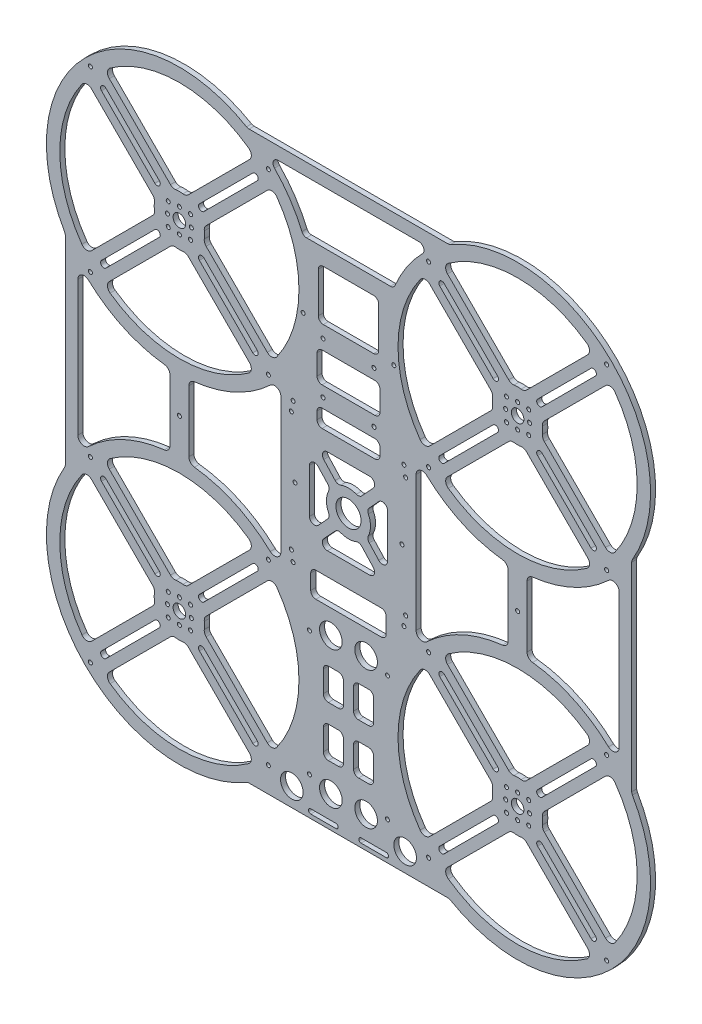
SolidWorks part; units mm, degrees
ref_plane "前视基准面" through (0, 0, 0) normal (0, 0, 1) x (1, 0, 0)
ref_plane "上视基准面" through (0, 0, 0) normal (0, 1, 0) x (1, 0, 0)
ref_plane "右视基准面" through (0, 0, 0) normal (1, 0, 0) x (0, 0, -1)
sketch "草图1" plane through (0, 0, 0) normal (0, 0, 1) x (1, 0, 0)
  line L1 (-155, 155) -> (155, 155)
  line L2 (-155, 155) -> (-155, -155)
  line L3 (-155, -155) -> (155, -155)
  line L4 (155, 155) -> (155, -155)
  line L5 (-155, 155) -> (155, -155) construction
  line L6 (-155, -155) -> (155, 155) construction
  point P0 (0, 0)
  dimension "D1" = 310
  dimension "D2" = 310
extrude "凸台-拉伸1" add sketch "草图1" along normal blind 4
sketch "草图2" plane through (0, 0, 4) normal (0, 0, 1) x (1, 0, 0)
  line L0 (-155, 0) -> (155, 0) construction
  line L1 (-155, 155) -> (-155, -155) construction
  line L2 (155, -155) -> (155, 155) construction
  line L3 (0, 155) -> (0, -155) construction
  line L4 (155, 155) -> (-155, 155) construction
  line L5 (-155, -155) -> (155, -155) construction
  line L6 (-155, -155) -> (155, 155) construction
  line L7 (-155, 155) -> (155, -155) construction
  line L8 (-134.3503, 134.3503) -> (134.3503, 134.3503) construction
  line L9 (-134.3503, 134.3503) -> (134.3503, 134.3503) construction
  line L10 (-134.3503, 134.3503) -> (-134.3503, -134.3503) construction
  line L11 (-134.3503, -134.3503) -> (134.3503, -134.3503) construction
  line L12 (134.3503, 134.3503) -> (134.3503, -134.3503) construction
  line L13 (-134.3503, 134.3503) -> (134.3503, -134.3503) construction
  line L14 (-134.3503, -134.3503) -> (134.3503, 134.3503) construction
  circle A0 centre (-134.3503, -134.3503) radius 20 construction
  circle A1 centre (-134.3503, -134.3503) radius 5
  circle A2 centre (-134.3503, -134.3503) radius 9.5 construction
  circle A3 centre (-134.3503, -143.8503) radius 1.6
  circle A4 centre (-143.8503, -134.3503) radius 1.6
  circle A5 centre (-134.3503, -124.8503) radius 1.6
  circle A6 centre (-124.8503, -134.3503) radius 1.6
  circle A7 centre (134.3503, -134.3503) radius 9.5 construction
  circle A8 centre (134.3503, -134.3503) radius 20 construction
  circle A9 centre (124.8503, -134.3503) radius 1.6
  circle A10 centre (134.3503, -124.8503) radius 1.6
  circle A11 centre (143.8503, -134.3503) radius 1.6
  circle A12 centre (134.3503, -143.8503) radius 1.6
  circle A13 centre (134.3503, -134.3503) radius 5
  circle A14 centre (134.3503, 134.3503) radius 20 construction
  circle A15 centre (134.3503, 134.3503) radius 9.5 construction
  circle A16 centre (-134.3503, 134.3503) radius 9.5 construction
  circle A17 centre (-134.3503, 134.3503) radius 20 construction
  circle A18 centre (134.3503, 134.3503) radius 5
  circle A19 centre (134.3503, 143.8503) radius 1.6
  circle A20 centre (143.8503, 134.3503) radius 1.6
  circle A21 centre (134.3503, 124.8503) radius 1.6
  circle A22 centre (124.8503, 134.3503) radius 1.6
  circle A23 centre (-124.8503, 134.3503) radius 1.6
  circle A24 centre (-134.3503, 124.8503) radius 1.6
  circle A25 centre (-143.8503, 134.3503) radius 1.6
  circle A26 centre (-134.3503, 143.8503) radius 1.6
  circle A27 centre (-134.3503, 134.3503) radius 5
  point P20 (0, 0)
  point P39 (-134.3503, -134.3503)
  point P48 (134.3503, -134.3503)
  point P71 (134.3503, 134.3503)
  point P72 (-134.3503, 134.3503)
  dimension "D3" = 40
  dimension "D4" = 10
  dimension "D5" = 19
  dimension "D6" = 3.2
  dimension "D8" = 19
  dimension "D9" = 9.5
  dimension "D1" = 380
  dimension "D2" = 268.7006
  dimension "D7" = 4
extrude "切除-拉伸2" cut sketch "草图2" against normal blind 4
sketch "草图3" plane through (0, 0, 4) normal (0, 0, 1) x (1, 0, 0)
  line L2 (-155, 0) -> (155, 0) construction
  line L3 (-155, 155) -> (-155, -155) construction
  line L4 (155, -155) -> (155, 155) construction
  line L5 (0, 155) -> (0, -155) construction
  line L6 (155, 155) -> (-155, 155) construction
  line L7 (-155, -155) -> (155, -155) construction
  circle A4 centre (0, 0) radius 2.5
  dimension "D1" = 5
extrude "切除-拉伸3" cut sketch "草图3" against normal blind 4
sketch "草图4" plane through (0, 0, 4) normal (0, 0, 1) x (1, 0, 0)
  circle A0 centre (0, 0) radius 10
  dimension "D1" = 20
extrude "切除-拉伸4" cut sketch "草图4" against normal blind 10
sketch "草图5" plane through (0, 0, 4) normal (0, 0, 1) x (1, 0, 0)
  line L0 (-155, 0) -> (155, 0) construction
  line L1 (-155, 155) -> (-155, -155) construction
  line L2 (155, -155) -> (155, 155) construction
  line L3 (0, 155) -> (0, -155) construction
  line L4 (155, 155) -> (-155, 155) construction
  line L5 (-155, -155) -> (155, -155) construction
  circle A0 centre (-42.5, 0) radius 1.6
  circle A1 centre (42.5, 0) radius 1.6
  dimension "D1" = 85
  dimension "D2" = 42.5
  dimension "D3" = 3.2
  dimension "D4" = 3.2
extrude "切除-拉伸5" cut sketch "草图5" against normal blind 10
sketch "草图7" plane through (0, 0, 4) normal (0, 0, 1) x (1, 0, 0)
  line L0 (0, 0) -> (0, 47.5) construction
  line L1 (-45.4, 47.5) -> (45.4, 47.5) construction
  line L2 (-45.4, 47.5) -> (-45.4, -47.5) construction
  line L3 (-45.4, -47.5) -> (45.4, -47.5) construction
  line L4 (45.4, 47.5) -> (45.4, -47.5) construction
  line L5 (-45.4, 47.5) -> (45.4, -47.5) construction
  line L6 (-45.4, -47.5) -> (45.4, 47.5) construction
  circle A0 centre (-45.4, 47.5) radius 1.6
  circle A1 centre (-45.4, -47.5) radius 1.6
  circle A2 centre (45.4, -47.5) radius 1.6
  circle A3 centre (45.4, 47.5) radius 1.6
  point P0 (0, 0)
  dimension "D3" = 3.2
  dimension "D4" = 3.2
  dimension "D1" = 90.8
  dimension "D2" = 95
extrude "切除-拉伸7" cut sketch "草图7" against normal blind 10
sketch "草图10" plane through (0, 0, 4) normal (0, 0, 1) x (1, 0, 0)
  line L0 (0, 0) -> (240, 0) construction
  line L1 (-240, 240) -> (240, 240) construction
  line L2 (-240, 240) -> (-240, -240) construction
  line L3 (-240, -240) -> (240, -240) construction
  line L4 (240, 240) -> (240, -240) construction
  line L5 (-240, 240) -> (240, -240) construction
  line L6 (-240, -240) -> (240, 240) construction
  line L7 (0, 0) -> (0, 155) construction
  line L8 (155, 155) -> (-155, 155) construction
  line L9 (155, -155) -> (155, 155) construction
  line L10 (155, -155) -> (-155, -155)
  line L11 (155, -155) -> (155, 155)
  line L12 (155, 155) -> (-155, 155)
  line L13 (-155, -155) -> (-155, 155)
  line L14 (155, -155) -> (-155, 155) construction
  line L15 (155, 155) -> (-155, -155) construction
  circle A0 centre (134.3503, 134.3503) radius 105.6497
  circle A1 centre (134.3503, 134.3503) radius 95
  circle A2 centre (134.3503, -134.3503) radius 95
  circle A4 centre (134.3503, -134.3503) radius 105.6497
  circle A5 centre (-134.3503, -134.3503) radius 95
  circle A6 centre (-134.3503, -134.3503) radius 105.6497
  circle A7 centre (-134.3503, 134.3503) radius 105.6497
  circle A8 centre (-134.3503, 134.3503) radius 95
  point P0 (0, 0)
  line M27 (155, 155) -> (-155, 155)
  dimension "D1" = 480
  dimension "D2" = 480
  dimension "D4" = 0
extrude "凸台-拉伸2" add sketch "草图10" against normal blind 4 contours A8 A7 L13 M27 | A6 L10 A5 L13 | L10 A4 L11 A2 | L12 A1 L11 A0 region at (145.061, -231.7224, 4) region at (-206.9633, -206.9633, 4) region at (157.9594, 36.18, 4) region at (-206.9633, 206.9633, 4)
sketch "草图11" plane through (0, 0, 4) normal (0, 0, 1) x (1, 0, 0)
  line L3 (-155, 0) -> (155, 0) construction
  line L6 (155, -30.7383) -> (155, 30.7383) construction
  line L7 (0, 155) -> (0, -155) construction
  line L8 (30.7383, 155) -> (-30.7383, 155) construction
  line L9 (-30.7383, -155) -> (30.7383, -155) construction
  line L10 (-134.3503, -134.3503) -> (134.3503, 134.3503) construction
  line L11 (-134.3503, 134.3503) -> (134.3503, -134.3503) construction
  line L21 (-155, 30.7383) -> (-155, -30.7383) construction
  line L23 (-225, 80.0871) -> (-225, -80.0871)
  line L25 (30.7383, -155) -> (-30.7383, -155)
  line L26 (-155, 30.7383) -> (-155, -30.7383)
  line L27 (-155, 30.7383) -> (-155, -30.7383)
  line L28 (80.0871, -225) -> (-80.0871, -225)
  line L29 (225, -80.0871) -> (225, 80.0871)
  line L30 (155, -30.7383) -> (155, 30.7383)
  line L31 (-30.7383, 155) -> (30.7383, 155)
  line L32 (-80.0871, 225) -> (80.0871, 225)
  arc A6 (-30.7383, 155) -> (-155, 30.7383) centre (-134.3503, 134.3503) ccw construction
  arc A7 (-155, -30.7383) -> (-30.7383, -155) centre (-134.3503, -134.3503) ccw construction
  arc A18 (80.0871, -225) -> (30.7383, -155) centre (134.3503, -134.3503) cw
  arc A19 (-30.7383, -155) -> (-80.0871, -225) centre (-134.3503, -134.3503) cw
  arc A20 (-155, -30.7383) -> (-30.7383, -155) centre (-134.3503, -134.3503) ccw
  arc A21 (-30.7383, 155) -> (-155, 30.7383) centre (-134.3503, 134.3503) ccw
  arc A22 (-155, -30.7383) -> (-225, -80.0871) centre (-134.3503, -134.3503) ccw
  arc A23 (-225, 80.0871) -> (-155, 30.7383) centre (-134.3503, 134.3503) ccw
  arc A24 (225, -80.0871) -> (155, -30.7383) centre (134.3503, -134.3503) ccw
  arc A25 (155, 30.7383) -> (225, 80.0871) centre (134.3503, 134.3503) ccw
  arc A26 (-80.0871, 225) -> (-30.7383, 155) centre (-134.3503, 134.3503) cw
  arc A27 (30.7383, 155) -> (80.0871, 225) centre (134.3503, 134.3503) cw
  dimension "D1" = 70
  dimension "D2" = 0
extrude "凸台-拉伸3" add sketch "草图11" against normal blind 4
sketch "草图12" plane through (0, 0, 4) normal (0, 0, 1) x (1, 0, 0)
  line L0 (-134.3503, -134.3503) -> (0, 0) construction
  line L1 (-74.6194, -60.4773) -> (-129.1739, -115.0318)
  line L2 (-60.4773, -74.6194) -> (-115.0318, -129.1739)
  line L3 (74.6194, -60.4773) -> (129.1739, -115.0318)
  line L4 (60.4773, -74.6194) -> (115.0318, -129.1739)
  line L5 (0, 0) -> (0, -225) construction
  line L6 (-80.0871, -225) -> (80.0871, -225) construction
  line L7 (60.4773, 74.6194) -> (115.0318, 129.1739)
  line L8 (0, 0) -> (225, 0) construction
  line L9 (225, -80.0871) -> (225, 80.0871) construction
  line L10 (74.6194, 60.4773) -> (129.1739, 115.0318)
  line L11 (-74.6194, 60.4773) -> (-129.1739, 115.0318)
  line L12 (-60.4773, 74.6194) -> (-115.0318, 129.1739)
  line L14 (-134.3503, 134.3503) -> (0, 0) construction
  arc A2 (-74.6194, -60.4773) -> (-60.4773, -74.6194) centre (-134.3503, -134.3503) ccw
  arc A3 (-129.1739, -115.0318) -> (-115.0318, -129.1739) centre (-134.3503, -134.3503) ccw
  arc A4 (74.6194, -60.4773) -> (60.4773, -74.6194) centre (134.3503, -134.3503) cw
  arc A5 (129.1739, -115.0318) -> (115.0318, -129.1739) centre (134.3503, -134.3503) cw
  arc A6 (74.6194, 60.4773) -> (60.4773, 74.6194) centre (134.3503, 134.3503) ccw
  arc A7 (129.1739, 115.0318) -> (115.0318, 129.1739) centre (134.3503, 134.3503) ccw
  arc A8 (-74.6194, 60.4773) -> (-60.4773, 74.6194) centre (-134.3503, 134.3503) cw
  arc A9 (-129.1739, 115.0318) -> (-115.0318, 129.1739) centre (-134.3503, 134.3503) cw
  dimension "D1" = 40
  dimension "D2" = 10
extrude "切除-拉伸12" cut sketch "草图12" against normal blind 6 contours L3 A5 L4 A4 | A6 L7 A7 L10 | L11 A9 L12 A8 | A3 L2 A2 L1
sketch "草图15" plane through (0, 0, 4) normal (0, 0, 1) x (1, 0, 0)
  line L10 (0, 0) -> (0, -225) construction
  line L11 (-80.0871, -225) -> (80.0871, -225) construction
  line L12 (0, 0) -> (225, 0) construction
  line L13 (225, -80.0871) -> (225, 80.0871) construction
  line L70 (60.4773, -74.6194) -> (115.0318, -129.1739) construction
  line L71 (74.6194, -60.4773) -> (129.1739, -115.0318) construction
  line L72 (194.0812, -60.4773) -> (139.5267, -115.0318)
  line L73 (208.2233, -74.6194) -> (153.6688, -129.1739)
  line L74 (208.2233, -194.0812) -> (153.6688, -139.5267)
  line L75 (194.0812, -208.2233) -> (139.5267, -153.6688)
  line L76 (74.6194, -208.2233) -> (129.1739, -153.6688)
  line L77 (60.4773, -194.0812) -> (115.0318, -139.5267)
  line L78 (-74.6194, -60.4773) -> (-129.1739, -115.0318) construction
  line L79 (-60.4773, -74.6194) -> (-115.0318, -129.1739) construction
  line L80 (-60.4773, -194.0812) -> (-115.0318, -139.5267)
  line L81 (-74.6194, -208.2233) -> (-129.1739, -153.6688)
  line L82 (-194.0812, -208.2233) -> (-139.5267, -153.6688)
  line L83 (-208.2233, -194.0812) -> (-153.6688, -139.5267)
  line L84 (-208.2233, -74.6194) -> (-153.6688, -129.1739)
  line L85 (-194.0812, -60.4773) -> (-139.5267, -115.0318)
  line L86 (-60.4773, 74.6194) -> (-115.0318, 129.1739) construction
  line L87 (-74.6194, 60.4773) -> (-129.1739, 115.0318) construction
  line L88 (74.6194, 60.4773) -> (129.1739, 115.0318) construction
  line L89 (60.4773, 74.6194) -> (115.0318, 129.1739) construction
  line L90 (-194.0812, 60.4773) -> (-139.5267, 115.0318)
  line L91 (-208.2233, 74.6194) -> (-153.6688, 129.1739)
  line L92 (-208.2233, 194.0812) -> (-153.6688, 139.5267)
  line L93 (-194.0812, 208.2233) -> (-139.5267, 153.6688)
  line L94 (-74.6194, 208.2233) -> (-129.1739, 153.6688)
  line L95 (-60.4773, 194.0812) -> (-115.0318, 139.5267)
  line L96 (60.4773, 194.0812) -> (115.0318, 139.5267)
  line L97 (74.6194, 208.2233) -> (129.1739, 153.6688)
  line L98 (194.0812, 208.2233) -> (139.5267, 153.6688)
  line L99 (208.2233, 194.0812) -> (153.6688, 139.5267)
  line L100 (208.2233, 74.6194) -> (153.6688, 129.1739)
  line L101 (194.0812, 60.4773) -> (139.5267, 115.0318)
  arc A66 (129.1739, -115.0318) -> (115.0318, -129.1739) centre (134.3503, -134.3503) ccw construction
  arc A67 (74.6194, -60.4773) -> (60.4773, -74.6194) centre (134.3503, -134.3503) ccw construction
  arc A68 (153.6688, -129.1739) -> (139.5267, -115.0318) centre (134.3503, -134.3503) ccw
  arc A69 (208.2233, -74.6194) -> (194.0812, -60.4773) centre (134.3503, -134.3503) ccw
  arc A70 (139.5267, -153.6688) -> (153.6688, -139.5267) centre (134.3503, -134.3503) ccw
  arc A71 (194.0812, -208.2233) -> (208.2233, -194.0812) centre (134.3503, -134.3503) ccw
  arc A72 (115.0318, -139.5267) -> (129.1739, -153.6688) centre (134.3503, -134.3503) ccw
  arc A73 (60.4773, -194.0812) -> (74.6194, -208.2233) centre (134.3503, -134.3503) ccw
  arc A74 (-74.6194, -60.4773) -> (-60.4773, -74.6194) centre (-134.3503, -134.3503) cw construction
  arc A75 (-129.1739, -115.0318) -> (-115.0318, -129.1739) centre (-134.3503, -134.3503) cw construction
  arc A76 (-60.4773, -194.0812) -> (-74.6194, -208.2233) centre (-134.3503, -134.3503) cw
  arc A77 (-115.0318, -139.5267) -> (-129.1739, -153.6688) centre (-134.3503, -134.3503) cw
  arc A78 (-194.0812, -208.2233) -> (-208.2233, -194.0812) centre (-134.3503, -134.3503) cw
  arc A79 (-139.5267, -153.6688) -> (-153.6688, -139.5267) centre (-134.3503, -134.3503) cw
  arc A80 (-208.2233, -74.6194) -> (-194.0812, -60.4773) centre (-134.3503, -134.3503) cw
  arc A81 (-153.6688, -129.1739) -> (-139.5267, -115.0318) centre (-134.3503, -134.3503) cw
  arc A82 (-129.1739, 115.0318) -> (-115.0318, 129.1739) centre (-134.3503, 134.3503) ccw construction
  arc A83 (-74.6194, 60.4773) -> (-60.4773, 74.6194) centre (-134.3503, 134.3503) ccw construction
  arc A84 (74.6194, 60.4773) -> (60.4773, 74.6194) centre (134.3503, 134.3503) cw construction
  arc A85 (129.1739, 115.0318) -> (115.0318, 129.1739) centre (134.3503, 134.3503) cw construction
  arc A86 (-153.6688, 129.1739) -> (-139.5267, 115.0318) centre (-134.3503, 134.3503) ccw
  arc A87 (-208.2233, 74.6194) -> (-194.0812, 60.4773) centre (-134.3503, 134.3503) ccw
  arc A88 (-139.5267, 153.6688) -> (-153.6688, 139.5267) centre (-134.3503, 134.3503) ccw
  arc A89 (-194.0812, 208.2233) -> (-208.2233, 194.0812) centre (-134.3503, 134.3503) ccw
  arc A90 (-115.0318, 139.5267) -> (-129.1739, 153.6688) centre (-134.3503, 134.3503) ccw
  arc A91 (-60.4773, 194.0812) -> (-74.6194, 208.2233) centre (-134.3503, 134.3503) ccw
  arc A92 (60.4773, 194.0812) -> (74.6194, 208.2233) centre (134.3503, 134.3503) cw
  arc A93 (115.0318, 139.5267) -> (129.1739, 153.6688) centre (134.3503, 134.3503) cw
  arc A94 (194.0812, 208.2233) -> (208.2233, 194.0812) centre (134.3503, 134.3503) cw
  arc A95 (139.5267, 153.6688) -> (153.6688, 139.5267) centre (134.3503, 134.3503) cw
  arc A96 (208.2233, 74.6194) -> (194.0812, 60.4773) centre (134.3503, 134.3503) cw
  arc A97 (153.6688, 129.1739) -> (139.5267, 115.0318) centre (134.3503, 134.3503) cw
  point P24 (134.3503, -134.3503)
  point P43 (-134.3503, -134.3503)
  point P78 (-134.3503, 134.3503)
  point P79 (134.3503, 134.3503)
  dimension "D1" = 4
extrude "凸台-拉伸4" add sketch "草图15" against normal blind 4
sketch "草图19" plane through (0, 0, 4) normal (0, 0, 1) x (1, 0, 0)
  line L1 (134.3503, -134.3503) -> (0, 0) construction
  line L2 (0, 225) -> (0, -225) construction
  line L3 (-80.0871, -225) -> (80.0871, -225) construction
  line L4 (0, 0) -> (225, 0) construction
  line L5 (225, -80.0871) -> (225, 80.0871) construction
  line L6 (-134.3503, -134.3503) -> (0, 0) construction
  line L7 (-134.3503, 134.3503) -> (0, 0) construction
  circle A0 centre (134.3503, -134.3503) radius 100 construction
  circle A1 centre (63.6396, -63.6396) radius 1.6
  circle A21 centre (205.061, -63.6396) radius 1.6
  circle A22 centre (205.061, -205.061) radius 1.6
  circle A23 centre (63.6396, -205.061) radius 1.6
  circle A24 centre (134.3503, -134.3503) radius 5 construction
  circle A25 centre (-134.3503, -134.3503) radius 100 construction
  circle A26 centre (-63.6396, -205.061) radius 1.6
  circle A27 centre (-205.061, -205.061) radius 1.6
  circle A28 centre (-205.061, -63.6396) radius 1.6
  circle A29 centre (-63.6396, -63.6396) radius 1.6
  circle A30 centre (-134.3503, 134.3503) radius 100 construction
  circle A31 centre (134.3503, 134.3503) radius 100 construction
  circle A32 centre (-63.6396, 63.6396) radius 1.6
  circle A33 centre (-205.061, 63.6396) radius 1.6
  circle A34 centre (-205.061, 205.061) radius 1.6
  circle A35 centre (-63.6396, 205.061) radius 1.6
  circle A36 centre (63.6396, 205.061) radius 1.6
  circle A37 centre (205.061, 205.061) radius 1.6
  circle A38 centre (205.061, 63.6396) radius 1.6
  circle A39 centre (63.6396, 63.6396) radius 1.6
  point P16 (134.3475, -134.9818)
  point P24 (134.3503, -134.3503)
  point P34 (-134.3503, -134.3503)
  point P35 (-134.3475, -134.9818)
  point P56 (-134.3475, 134.9818)
  point P57 (-134.3503, 134.3503)
  point P58 (134.3503, 134.3503)
  point P59 (134.3475, 134.9818)
  dimension "D1" = 200
  dimension "D2" = 3.2
  dimension "D5" = 141.4214
  dimension "D4" = 100
  dimension "D3" = 4
extrude "切除-拉伸13" cut sketch "草图19" against normal blind 6
sketch "草图20" plane through (0, 0, 4) normal (0, 0, 1) x (1, 0, 0)
  line L0 (0, 0) -> (0, -225) construction
  line L1 (-80.0871, -225) -> (80.0871, -225) construction
  line L3 (-31, -96) -> (31, -96) construction
  line L4 (-31, -96) -> (-31, -195) construction
  line L5 (-31, -195) -> (31, -195) construction
  line L6 (31, -96) -> (31, -195) construction
  line L7 (-31, -96) -> (31, -195) construction
  line L8 (-31, -195) -> (31, -96) construction
  circle A0 centre (-31, -195) radius 1.6
  circle A1 centre (-31, -96) radius 1.6
  circle A2 centre (31, -195) radius 1.6
  circle A3 centre (31, -96) radius 1.6
  point P5 (0, -145.5)
  dimension "D4" = 3.2
  dimension "D5" = 3.2
  dimension "D1" = 99
  dimension "D2" = 62
  dimension "D3" = 30
extrude "切除-拉伸14" cut sketch "草图20" against normal blind 10
sketch "草图21" plane through (0, 0, 4) normal (0, 0, 1) x (1, 0, 0)
  line L0 (-225, 0) -> (225, 0) construction
  line L1 (-225, 80.0871) -> (-225, -80.0871) construction
  line L2 (225, -80.0871) -> (225, 80.0871) construction
  line L3 (0, 225) -> (0, -225) construction
  line L4 (80.0871, 225) -> (-80.0871, 225) construction
  line L5 (-80.0871, -225) -> (80.0871, -225) construction
  line L6 (-215, 66.1045) -> (-215, -66.1045)
  line L7 (-134.3503, 134.3503) -> (-134.3503, -134.3503) construction
  line L8 (-141.8503, 28.9671) -> (-141.8503, -28.9671)
  line L9 (-53.7006, 66.1045) -> (-53.7006, -66.1045)
  line L10 (-126.8503, 28.9671) -> (-126.8503, -28.9671)
  line L11 (-134.3503, -134.3503) -> (134.3503, 134.3503) construction
  line L12 (126.8503, 28.9671) -> (126.8503, -28.9671)
  line L13 (53.7006, 66.1045) -> (53.7006, -66.1045)
  line L14 (141.8503, 28.9671) -> (141.8503, -28.9671)
  line L15 (215, 66.1045) -> (215, -66.1045)
  arc A1 (-215, 66.1045) -> (-141.8503, 28.9671) centre (-134.3503, 134.3503) ccw
  arc A2 (-53.7006, -66.1045) -> (-126.8503, -28.9671) centre (-134.3503, -134.3503) ccw
  arc A3 (-141.8503, -28.9671) -> (-215, -66.1045) centre (-134.3503, -134.3503) ccw
  arc A4 (-126.8503, 28.9671) -> (-53.7006, 66.1045) centre (-134.3503, 134.3503) ccw
  arc A5 (126.8503, 28.9671) -> (53.7006, 66.1045) centre (134.3503, 134.3503) cw
  arc A6 (53.7006, -66.1045) -> (126.8503, -28.9671) centre (134.3503, -134.3503) cw
  arc A7 (215, 66.1045) -> (141.8503, 28.9671) centre (134.3503, 134.3503) cw
  arc A8 (141.8503, -28.9671) -> (215, -66.1045) centre (134.3503, -134.3503) cw
  dimension "D1" = 10
  dimension "D2" = 7.5
extrude "切除-拉伸15" cut sketch "草图21" against normal blind 10
fillet "圆角1" radius 5 80 edges at (-60.4773, 74.6194, 2) (-115.0318, 129.1739, 2) (-115.0318, 139.5267, 2) (-60.4773, 194.0812, 2) (129.1739, 115.0318, 2) (139.5267, 115.0318, 2) (194.0812, 60.4773, 2) (74.6194, 60.4773, 2) (-129.1739, -115.0318, 2) (-139.5267, -115.0318, 2) (-194.0812, -60.4773, 2) (-74.6194, -60.4773, 2) (60.4773, -74.6194, 2) (115.0318, -129.1739, 2) (115.0318, -139.5267, 2) (60.4773, -194.0812, 2) (139.5267, -115.0318, 2) (129.1739, -115.0318, 2) (74.6194, -60.4773, 2) (194.0812, -60.4773, 2) (153.6688, -139.5267, 2) (153.6688, -129.1739, 2) (208.2233, -74.6194, 2) (208.2233, -194.0812, 2) (129.1739, -153.6688, 2) (139.5267, -153.6688, 2) (194.0812, -208.2233, 2) (74.6194, -208.2233, 2) (-115.0318, -139.5267, 2) (-115.0318, -129.1739, 2) (-60.4773, -74.6194, 2) (-60.4773, -194.0812, 2) (-139.5267, -153.6688, 2) (-129.1739, -153.6688, 2) (-74.6194, -208.2233, 2) (-194.0812, -208.2233, 2) (-153.6688, -129.1739, 2) (-153.6688, -139.5267, 2) (-208.2233, -194.0812, 2) (-208.2233, -74.6194, 2) (-139.5267, 115.0318, 2) (-129.1739, 115.0318, 2) (-74.6194, 60.4773, 2) (-194.0812, 60.4773, 2) (-153.6688, 129.1739, 2) (-208.2233, 74.6194, 2) (-208.2233, 194.0812, 2) (-129.1739, 153.6688, 2) (-139.5267, 153.6688, 2) (-194.0812, 208.2233, 2) (-74.6194, 208.2233, 2) (115.0318, 139.5267, 2) (115.0318, 129.1739, 2) (60.4773, 74.6194, 2) (60.4773, 194.0812, 2) (139.5267, 153.6688, 2) (129.1739, 153.6688, 2) (74.6194, 208.2233, 2) (194.0812, 208.2233, 2) (153.6688, 129.1739, 2) (153.6688, 139.5267, 2) (208.2233, 194.0812, 2) (208.2233, 74.6194, 2) (126.8503, -28.9671, 2) (53.7006, -66.1045, 2) (53.7006, 66.1045, 2) (126.8503, 28.9671, 2) (-141.8503, -28.9671, 2) (-215, -66.1045, 2) (-215, 66.1045, 2) (-141.8503, 28.9671, 2) (-53.7006, -66.1045, 2) (-126.8503, -28.9671, 2) (-126.8503, 28.9671, 2) (-53.7006, 66.1045, 2) (215, -66.1045, 2) (141.8503, -28.9671, 2) (141.8503, 28.9671, 2) (215, 66.1045, 2) (-153.6688, 139.5267, 2)
sketch "草图24" plane through (0, 0, 4) normal (0, 0, 1) x (1, 0, 0)
  line L0 (-225, 0) -> (225, 0) construction
  line L1 (-225, 80.0871) -> (-225, -80.0871) construction
  line L2 (225, -80.0871) -> (225, 80.0871) construction
  line L3 (0, 225) -> (0, -225) construction
  line L4 (80.0871, 225) -> (-80.0871, 225) construction
  line L5 (-80.0871, -225) -> (80.0871, -225) construction
  line L6 (-205.061, -205.061) -> (-134.3503, -134.3503) construction
  line L7 (-194.4544, -194.4544) -> (-152.028, -152.028) construction
  line L8 (-196.2221, -192.6866) -> (-153.7957, -150.2602)
  line L9 (-192.6866, -196.2221) -> (-150.2602, -153.7957)
  line L10 (-196.2221, -76.014) -> (-153.7957, -118.4404)
  line L11 (-192.6866, -72.4784) -> (-150.2602, -114.9049)
  line L12 (-194.4544, -74.2462) -> (-152.028, -116.6726) construction
  line L13 (-76.014, -72.4784) -> (-118.4404, -114.9049)
  line L14 (-72.4784, -76.014) -> (-114.9049, -118.4404)
  line L15 (-74.2462, -74.2462) -> (-116.6726, -116.6726) construction
  line L16 (-72.4784, -192.6866) -> (-114.9049, -150.2602)
  line L17 (-76.014, -196.2221) -> (-118.4404, -153.7957)
  line L18 (-74.2462, -194.4544) -> (-116.6726, -152.028) construction
  line L19 (205.061, -205.061) -> (134.3503, -134.3503) construction
  line L20 (74.2462, -194.4544) -> (116.6726, -152.028) construction
  line L21 (76.014, -196.2221) -> (118.4404, -153.7957)
  line L22 (72.4784, -192.6866) -> (114.9049, -150.2602)
  line L23 (74.2462, -74.2462) -> (116.6726, -116.6726) construction
  line L24 (72.4784, -76.014) -> (114.9049, -118.4404)
  line L25 (76.014, -72.4784) -> (118.4404, -114.9049)
  line L26 (194.4544, -74.2462) -> (152.028, -116.6726) construction
  line L27 (192.6866, -72.4784) -> (150.2602, -114.9049)
  line L28 (196.2221, -76.014) -> (153.7957, -118.4404)
  line L29 (194.4544, -194.4544) -> (152.028, -152.028) construction
  line L30 (196.2221, -192.6866) -> (153.7957, -150.2602)
  line L31 (192.6866, -196.2221) -> (150.2602, -153.7957)
  line L32 (205.061, 205.061) -> (134.3503, 134.3503) construction
  line L33 (-205.061, 205.061) -> (-134.3503, 134.3503) construction
  line L34 (194.4544, 194.4544) -> (152.028, 152.028) construction
  line L35 (196.2221, 192.6866) -> (153.7957, 150.2602)
  line L36 (192.6866, 196.2221) -> (150.2602, 153.7957)
  line L37 (194.4544, 74.2462) -> (152.028, 116.6726) construction
  line L38 (192.6866, 72.4784) -> (150.2602, 114.9049)
  line L39 (196.2221, 76.014) -> (153.7957, 118.4404)
  line L40 (74.2462, 74.2462) -> (116.6726, 116.6726) construction
  line L41 (72.4784, 76.014) -> (114.9049, 118.4404)
  line L42 (76.014, 72.4784) -> (118.4404, 114.9049)
  line L43 (74.2462, 194.4544) -> (116.6726, 152.028) construction
  line L44 (76.014, 196.2221) -> (118.4404, 153.7957)
  line L45 (72.4784, 192.6866) -> (114.9049, 150.2602)
  line L46 (-74.2462, 194.4544) -> (-116.6726, 152.028) construction
  line L47 (-76.014, 196.2221) -> (-118.4404, 153.7957)
  line L48 (-72.4784, 192.6866) -> (-114.9049, 150.2602)
  line L49 (-74.2462, 74.2462) -> (-116.6726, 116.6726) construction
  line L50 (-72.4784, 76.014) -> (-114.9049, 118.4404)
  line L51 (-76.014, 72.4784) -> (-118.4404, 114.9049)
  line L52 (-194.4544, 74.2462) -> (-152.028, 116.6726) construction
  line L53 (-192.6866, 72.4784) -> (-150.2602, 114.9049)
  line L54 (-196.2221, 76.014) -> (-153.7957, 118.4404)
  line L55 (-194.4544, 194.4544) -> (-152.028, 152.028) construction
  line L56 (-196.2221, 192.6866) -> (-153.7957, 150.2602)
  line L57 (-192.6866, 196.2221) -> (-150.2602, 153.7957)
  circle A0 centre (-134.3503, -134.3503) radius 20 construction
  arc A1 (-196.2221, -192.6866) -> (-192.6866, -196.2221) centre (-194.4544, -194.4544) ccw
  arc A2 (-150.2602, -153.7957) -> (-153.7957, -150.2602) centre (-152.028, -152.028) ccw
  circle A3 centre (-134.3503, -134.3503) radius 5 construction
  circle A4 centre (-205.061, -205.061) radius 1.6 construction
  arc A5 (-192.6866, -72.4784) -> (-196.2221, -76.014) centre (-194.4544, -74.2462) ccw
  arc A6 (-153.7957, -118.4404) -> (-150.2602, -114.9049) centre (-152.028, -116.6726) ccw
  arc A7 (-72.4784, -76.014) -> (-76.014, -72.4784) centre (-74.2462, -74.2462) ccw
  arc A8 (-118.4404, -114.9049) -> (-114.9049, -118.4404) centre (-116.6726, -116.6726) ccw
  arc A9 (-76.014, -196.2221) -> (-72.4784, -192.6866) centre (-74.2462, -194.4544) ccw
  arc A10 (-114.9049, -150.2602) -> (-118.4404, -153.7957) centre (-116.6726, -152.028) ccw
  circle A11 centre (134.3503, -134.3503) radius 20 construction
  arc A12 (76.014, -196.2221) -> (72.4784, -192.6866) centre (74.2462, -194.4544) cw
  arc A13 (114.9049, -150.2602) -> (118.4404, -153.7957) centre (116.6726, -152.028) cw
  arc A14 (72.4784, -76.014) -> (76.014, -72.4784) centre (74.2462, -74.2462) cw
  arc A15 (118.4404, -114.9049) -> (114.9049, -118.4404) centre (116.6726, -116.6726) cw
  arc A16 (192.6866, -72.4784) -> (196.2221, -76.014) centre (194.4544, -74.2462) cw
  arc A17 (153.7957, -118.4404) -> (150.2602, -114.9049) centre (152.028, -116.6726) cw
  arc A18 (196.2221, -192.6866) -> (192.6866, -196.2221) centre (194.4544, -194.4544) cw
  arc A19 (150.2602, -153.7957) -> (153.7957, -150.2602) centre (152.028, -152.028) cw
  circle A20 centre (134.3503, 134.3503) radius 20 construction
  circle A21 centre (-134.3503, 134.3503) radius 20 construction
  arc A22 (196.2221, 192.6866) -> (192.6866, 196.2221) centre (194.4544, 194.4544) ccw
  arc A23 (150.2602, 153.7957) -> (153.7957, 150.2602) centre (152.028, 152.028) ccw
  arc A24 (192.6866, 72.4784) -> (196.2221, 76.014) centre (194.4544, 74.2462) ccw
  arc A25 (153.7957, 118.4404) -> (150.2602, 114.9049) centre (152.028, 116.6726) ccw
  arc A26 (72.4784, 76.014) -> (76.014, 72.4784) centre (74.2462, 74.2462) ccw
  arc A27 (118.4404, 114.9049) -> (114.9049, 118.4404) centre (116.6726, 116.6726) ccw
  arc A28 (76.014, 196.2221) -> (72.4784, 192.6866) centre (74.2462, 194.4544) ccw
  arc A29 (114.9049, 150.2602) -> (118.4404, 153.7957) centre (116.6726, 152.028) ccw
  arc A30 (-76.014, 196.2221) -> (-72.4784, 192.6866) centre (-74.2462, 194.4544) cw
  arc A31 (-114.9049, 150.2602) -> (-118.4404, 153.7957) centre (-116.6726, 152.028) cw
  arc A32 (-72.4784, 76.014) -> (-76.014, 72.4784) centre (-74.2462, 74.2462) cw
  arc A33 (-118.4404, 114.9049) -> (-114.9049, 118.4404) centre (-116.6726, 116.6726) cw
  arc A34 (-192.6866, 72.4784) -> (-196.2221, 76.014) centre (-194.4544, 74.2462) cw
  arc A35 (-153.7957, 118.4404) -> (-150.2602, 114.9049) centre (-152.028, 116.6726) cw
  arc A36 (-196.2221, 192.6866) -> (-192.6866, 196.2221) centre (-194.4544, 194.4544) cw
  arc A37 (-150.2602, 153.7957) -> (-153.7957, 150.2602) centre (-152.028, 152.028) cw
  point P19 (-173.2412, -173.2412)
  point P33 (-173.2412, -95.4594)
  point P40 (-95.4594, -95.4594)
  point P47 (-95.4594, -173.2412)
  point P52 (-134.3503, -134.3503)
  point P53 (134.3503, -134.3503)
  point P56 (95.4594, -173.2412)
  point P63 (95.4594, -95.4594)
  point P70 (173.2412, -95.4594)
  point P77 (173.2412, -173.2412)
  point P90 (173.2412, 173.2412)
  point P97 (173.2412, 95.4594)
  point P104 (95.4594, 95.4594)
  point P111 (95.4594, 173.2412)
  point P116 (134.3503, 134.3503)
  point P117 (-134.3503, 134.3503)
  point P120 (-95.4594, 173.2412)
  point P127 (-95.4594, 95.4594)
  point P134 (-173.2412, 95.4594)
  point P141 (-173.2412, 173.2412)
  dimension "D1" = 40
  dimension "D2" = 2.5
  dimension "D3" = 25
  dimension "D4" = 15
  dimension "D6" = 17.6777
  dimension "D7" = 17.6777
  dimension "D5" = 4
extrude "切除-拉伸16" cut sketch "草图24" against normal blind 10
sketch "草图25" plane through (0, 0, 4) normal (0, 0, 1) x (1, 0, 0)
  line L0 (-63.6396, -205.061) -> (63.6396, -205.061) construction
  line L1 (0, -225) -> (0, 225) construction
  line L2 (-80.0871, -225) -> (80.0871, -225) construction
  line L3 (80.0871, 225) -> (-80.0871, 225) construction
  line L4 (-30, -220) -> (-10, -220) construction
  line L5 (-30, -218.2) -> (-10, -218.2)
  line L6 (-30, -221.8) -> (-10, -221.8)
  line L7 (30, -220) -> (10, -220) construction
  line L8 (30, -218.2) -> (10, -218.2)
  line L9 (30, -221.8) -> (10, -221.8)
  arc A1 (-30, -218.2) -> (-30, -221.8) centre (-30, -220) ccw
  arc A2 (-10, -221.8) -> (-10, -218.2) centre (-10, -220) ccw
  arc A3 (30, -218.2) -> (30, -221.8) centre (30, -220) cw
  arc A4 (10, -221.8) -> (10, -218.2) centre (10, -220) cw
  point P12 (-20, -220)
  point P19 (20, -220)
  dimension "D1" = 1.8
  dimension "D2" = 10
  dimension "D3" = 5
  dimension "D4" = 20
extrude "切除-拉伸17" cut sketch "草图25" against normal blind 5
sketch "草图26" plane through (0, 0, 4) normal (0, 0, 1) x (1, 0, 0)
  line L0 (0, 225) -> (0, -225) construction
  line L1 (80.0871, 225) -> (-80.0871, 225) construction
  line L2 (-80.0871, -225) -> (80.0871, -225) construction
  line L3 (-225, 0) -> (225, 0) construction
  line L4 (-225, 80.0871) -> (-225, -80.0871) construction
  line L5 (225, -80.0871) -> (225, 80.0871) construction
  line L7 (-20.25, 110.25) -> (20.25, 110.25) construction
  line L8 (-20.25, 110.25) -> (-20.25, 69.75) construction
  line L9 (-20.25, 69.75) -> (20.25, 69.75) construction
  line L10 (20.25, 110.25) -> (20.25, 69.75) construction
  line L11 (-20.25, 110.25) -> (20.25, 69.75) construction
  line L12 (-20.25, 69.75) -> (20.25, 110.25) construction
  circle A0 centre (-20.25, 69.75) radius 1.6
  circle A1 centre (-20.25, 110.25) radius 1.6
  circle A2 centre (20.25, 69.75) radius 1.6
  circle A3 centre (20.25, 110.25) radius 1.6
  circle A4 centre (-36, 120) radius 1.6
  circle A5 centre (36, 120) radius 1.6
  point P12 (0, 90)
  dimension "D4" = 3.2
  dimension "D5" = 3.2
  dimension "D6" = 36
  dimension "D7" = 3.2
  dimension "D8" = 120
  dimension "D1" = 90
  dimension "D2" = 40.5
  dimension "D3" = 40.5
extrude "切除-拉伸18" cut sketch "草图26" against normal blind 10
sketch "草图27" plane through (0, 0, 4) normal (0, 0, 1) x (1, 0, 0)
  line L0 (-225, 0) -> (225, 0) construction
  line L1 (-225, 80.0871) -> (-225, -80.0871) construction
  line L2 (225, -80.0871) -> (225, 80.0871) construction
  line L3 (0, 225) -> (0, -225) construction
  line L4 (80.0871, 225) -> (-80.0871, 225) construction
  line L5 (-80.0871, -225) -> (80.0871, -225) construction
  line L6 (-126.8503, 24.4089) -> (-126.8503, -24.4089) construction
  line L7 (-31, -96) -> (31, -195) construction
  line L8 (0, -145.5) -> (20, -145.5) construction
  line L9 (-20, -138) -> (20, -138) construction
  line L10 (-20, -138) -> (-20, -153) construction
  line L11 (-20, -153) -> (20, -153) construction
  line L12 (20, -138) -> (20, -153) construction
  line L13 (-20, -138) -> (20, -153) construction
  line L14 (-20, -153) -> (20, -138) construction
  line L15 (-31, 27.7529) -> (-31, -27.7529)
  line L16 (-20, -178) -> (20, -178)
  line L17 (-20, -178) -> (-20, -153)
  line L18 (-20, -153) -> (20, -153)
  line L19 (20, -178) -> (20, -153)
  line L20 (-20, -178) -> (20, -153) construction
  line L21 (-20, -153) -> (20, -178) construction
  line L22 (-35, 38) -> (35, 38) construction
  line L23 (-35, 38) -> (-35, -38) construction
  line L24 (-35, -38) -> (35, -38) construction
  line L25 (35, 38) -> (35, -38) construction
  line L26 (-35, 38) -> (35, -38) construction
  line L27 (-35, -38) -> (35, 38) construction
  line L28 (-31, 27.7529) -> (-14.4841, 9.8214)
  line L29 (-31, -27.7529) -> (-14.4841, -9.8214)
  line L30 (-25.8776, -34) -> (25.8776, -34)
  line L31 (-25.8776, -34) -> (-8.5998, -15.2412)
  line L32 (25.8776, -34) -> (8.5998, -15.2412)
  line L33 (31, -27.7529) -> (14.4841, -9.8214)
  line L34 (31, 27.7529) -> (14.4841, 9.8214)
  line L35 (31, 27.7529) -> (31, -27.7529)
  line L36 (25.8776, 34) -> (8.5998, 15.2412)
  line L37 (-25.8776, 34) -> (25.8776, 34)
  line L38 (-25.8776, 34) -> (-8.5998, 15.2412)
  line L39 (-20, -138) -> (20, -138)
  line L40 (20, -113) -> (20, -138)
  line L41 (-20, -113) -> (20, -113)
  line L42 (-20, -113) -> (-20, -138)
  line L44 (-30, -52) -> (30, -52)
  line L45 (-30, -52) -> (-30, -72)
  line L46 (-30, -72) -> (30, -72)
  line L47 (30, -52) -> (30, -72)
  line L48 (-30, -52) -> (30, -72) construction
  line L49 (-30, -72) -> (30, -52) construction
  circle A0 centre (-134.3503, 0) radius 1.6
  circle A1 centre (134.3503, 0) radius 1.6
  circle A2 centre (-45, -210) radius 9
  circle A3 centre (-14, -200) radius 9
  circle A4 centre (14, -200) radius 9
  circle A5 centre (45, -210) radius 9
  circle A6 centre (14, -91) radius 9
  circle A7 centre (-14, -91) radius 9
  arc A8 (-14.4841, 9.8214) -> (-14.4841, -9.8214) centre (0, 0) ccw
  arc A9 (8.5998, 15.2412) -> (-8.5998, 15.2412) centre (0, 0) ccw
  arc A10 (14.4841, -9.8214) -> (14.4841, 9.8214) centre (0, 0) ccw
  arc A11 (-8.5998, -15.2412) -> (8.5998, -15.2412) centre (0, 0) ccw
  point P26 (0, -145.5)
  point P33 (0, -165.5)
  point P45 (0, 0)
  point P58 (-31, 0)
  point P62 (0, -34)
  point P72 (0, -62)
  dimension "D1" = 7.5
  dimension "D2" = 3.2
  dimension "D3" = 15
  dimension "D4" = 45
  dimension "D5" = 14
  dimension "D6" = 25
  dimension "D7" = 18
  dimension "D8" = 18
  dimension "D14" = 35
  dimension "D9" = 15
  dimension "D10" = 40
  dimension "D11" = 25
  dimension "D12" = 70
  dimension "D13" = 76
  dimension "D15" = 4
  dimension "D16" = 4
  dimension "D17" = 4
  dimension "D18" = 20
  dimension "D19" = 62
  dimension "D20" = 60
extrude "切除-拉伸19" cut sketch "草图27" against normal blind 10
fillet "圆角3" radius 4 28 edges at (20, -113, 2) (20, -138, 2) (-20, -138, 2) (-20, -113, 2) (-20, -178, 2) (-20, -153, 2) (20, -153, 2) (20, -178, 2) (-30, -72, 2) (30, -52, 2) (30, -72, 2) (8.5998, 15.2412, 2) (-8.5998, 15.2412, 2) (-25.8776, 34, 2) (25.8776, 34, 2) (-14.4841, -9.8214, 2) (-31, -27.7529, 2) (-31, 27.7529, 2) (-14.4841, 9.8214, 2) (14.4841, -9.8214, 2) (14.4841, 9.8214, 2) (31, 27.7529, 2) (31, -27.7529, 2) (8.5998, -15.2412, 2) (25.8776, -34, 2) (-25.8776, -34, 2) (-8.5998, -15.2412, 2) (-30, -52, 2)
sketch "草图29" plane through (0, 0, 4) normal (0, 0, 1) x (1, 0, 0)
  line L3 (-36.024, 173) -> (36.024, 173)
  line L4 (66.1045, 215) -> (-66.1045, 215)
  arc A2 (-36.024, 173) -> (-66.1045, 215) centre (-134.3503, 134.3503) ccw
  arc A3 (66.1045, 215) -> (36.024, 173) centre (134.3503, 134.3503) ccw
extrude "切除-拉伸21" cut sketch "草图29" against normal blind 10
sketch "草图30" plane through (0, 0, 4) normal (0, 0, 1) x (1, 0, 0)
  line L0 (0, 0) -> (0, -225) construction
  line L1 (-80.0871, -225) -> (80.0871, -225) construction
  line L2 (-16, -178) -> (16, -178) construction
  line L3 (-4, -113) -> (4, -113)
  line L4 (-4, -113) -> (-4, -178)
  line L5 (-4, -178) -> (4, -178)
  line L6 (4, -113) -> (4, -178)
  line L7 (-4, -113) -> (4, -178) construction
  line L8 (-4, -178) -> (4, -113) construction
  line L9 (16, -113) -> (-16, -113) construction
  point P5 (0, -145.5)
  dimension "D1" = 0
  dimension "D2" = 8
extrude "凸台-拉伸5" add sketch "草图30" against normal blind 4
fillet "圆角4" radius 4 8 edges at (4, -178, 2) (4, -153, 2) (-4, -138, 2) (-4, -178, 2) (-4, -153, 2) (4, -113, 2) (4, -138, 2) (-4, -113, 2)
sketch "草图31" plane through (0, 0, 4) normal (0, 0, 1) x (1, 0, 0)
  line L0 (-225, 0) -> (225, 0) construction
  line L1 (-225, 80.0871) -> (-225, -80.0871) construction
  line L2 (225, -80.0871) -> (225, 80.0871) construction
  line L3 (0, 173) -> (0, -225) construction
  line L4 (-36.024, 173) -> (36.024, 173) construction
  line L5 (-80.0871, -225) -> (80.0871, -225) construction
  line L6 (-20.25, 110.25) -> (20.25, 69.75) construction
  line L8 (-25, 102) -> (25, 102)
  line L9 (-25, 102) -> (-25, 78)
  line L10 (-25, 78) -> (25, 78)
  line L11 (25, 102) -> (25, 78)
  line L12 (-25, 102) -> (25, 78) construction
  line L13 (-25, 78) -> (25, 102) construction
  line L14 (-24, 160) -> (24, 160)
  line L15 (-24, 160) -> (-24, 120)
  line L16 (-24, 120) -> (24, 120)
  line L17 (24, 160) -> (24, 120)
  line L18 (-24, 160) -> (24, 120) construction
  line L19 (-24, 120) -> (24, 160) construction
  line L20 (-25, 62) -> (25, 62)
  line L21 (-25, 62) -> (-25, 48)
  line L22 (-25, 48) -> (25, 48)
  line L23 (25, 62) -> (25, 48)
  line L24 (-25, 62) -> (25, 48) construction
  line L25 (-25, 48) -> (25, 62) construction
  point P16 (0, 90)
  point P21 (0, 140)
  point P26 (0, 55)
  dimension "D1" = 24
  dimension "D2" = 50
  dimension "D3" = 140
  dimension "D4" = 40
  dimension "D5" = 48
  dimension "D6" = 50
  dimension "D7" = 14
  dimension "D8" = 55
extrude "切除-拉伸22" cut sketch "草图31" against normal blind 4
fillet "圆角5" radius 4 8 edges at (-24, 120, 2) (-24, 160, 2) (24, 160, 2) (24, 120, 2) (-25, 78, 2) (25, 102, 2) (25, 78, 2) (-25, 102, 2)
fillet "圆角6" radius 4 8 edges at (-225, 80.0871, 2) (-225, -80.0871, 2) (-80.0871, -225, 2) (80.0871, -225, 2) (225, -80.0871, 2) (225, 80.0871, 2) (36.024, 173, 2) (-36.024, 173, 2)
fillet "圆角7" radius 4 4 edges at (80.0871, 225, 2) (-80.0871, 225, 2) (66.1045, 215, 2) (-66.1045, 215, 2)
fillet "圆角8" radius 4 4 edges at (-25, 48, 2) (25, 62, 2) (25, 48, 2) (-25, 62, 2)
sketch "草图32" plane through (0, 0, 4) normal (0, 0, 1) x (1, 0, 0)
  line L0 (0, 225) -> (0, -225) construction
  line L1 (78.9924, 225) -> (-78.9924, 225) construction
  line L2 (-78.9924, -225) -> (78.9924, -225) construction
  line L3 (-225, 0) -> (225, 0) construction
  line L4 (-225, 78.9924) -> (-225, -78.9924) construction
  line L5 (225, -78.9924) -> (225, 78.9924) construction
  line L6 (0, 0) -> (134.3503, 134.3503) construction
  line L7 (121.8503, 134.3503) -> (134.3503, 134.3503) construction
  line L8 (134.3503, 134.3503) -> (134.3503, 121.8503) construction
  line L9 (-134.3503, 134.3503) -> (-134.3503, 121.8503) construction
  line L10 (-121.8503, 134.3503) -> (-134.3503, 134.3503) construction
  line L11 (-121.8503, -134.3503) -> (-134.3503, -134.3503) construction
  line L12 (-134.3503, -134.3503) -> (-134.3503, -121.8503) construction
  line L13 (134.3503, -134.3503) -> (134.3503, -121.8503) construction
  line L14 (121.8503, -134.3503) -> (134.3503, -134.3503) construction
  circle A0 centre (134.3503, 134.3503) radius 12.5 construction
  circle A1 centre (125.5115, 125.5115) radius 1.6
  circle A2 centre (143.1891, 125.5115) radius 1.6
  circle A3 centre (143.1891, 143.1891) radius 1.6
  circle A4 centre (125.5115, 143.1891) radius 1.6
  circle A5 centre (-134.3503, 134.3503) radius 12.5 construction
  circle A6 centre (-125.5115, 143.1891) radius 1.6
  circle A7 centre (-143.1891, 143.1891) radius 1.6
  circle A8 centre (-143.1891, 125.5115) radius 1.6
  circle A9 centre (-125.5115, 125.5115) radius 1.6
  circle A10 centre (-134.3503, -134.3503) radius 12.5 construction
  circle A11 centre (134.3503, -134.3503) radius 12.5 construction
  circle A12 centre (-125.5115, -125.5115) radius 1.6
  circle A13 centre (-143.1891, -125.5115) radius 1.6
  circle A14 centre (-143.1891, -143.1891) radius 1.6
  circle A15 centre (-125.5115, -143.1891) radius 1.6
  circle A16 centre (125.5115, -143.1891) radius 1.6
  circle A17 centre (143.1891, -143.1891) radius 1.6
  circle A18 centre (143.1891, -125.5115) radius 1.6
  circle A19 centre (125.5115, -125.5115) radius 1.6
  dimension "D1" = 25
  dimension "D2" = 3.2
extrude "切除-拉伸23" cut sketch "草图32" against normal blind 10
sketch "草图33" plane through (0, 0, 4) normal (0, 0, 1) x (1, 0, 0)
  line L0 (0, 55.5) -> (0, -55.5) construction
  line L1 (-44, 55.5) -> (44, 55.5) construction
  line L2 (-44, 55.5) -> (-44, -55.5) construction
  line L3 (-44, -55.5) -> (44, -55.5) construction
  line L4 (44, 55.5) -> (44, -55.5) construction
  line L5 (-44, 55.5) -> (44, -55.5) construction
  line L6 (-44, -55.5) -> (44, 55.5) construction
  line L7 (-44, 55.5) -> (-44, -55.5) construction
  circle A0 centre (44, -55.5) radius 1.6
  circle A1 centre (44, 55.5) radius 1.6
  circle A2 centre (-44, 55.5) radius 1.6
  circle A3 centre (-44, -55.5) radius 1.6
  point P0 (0, 0)
  dimension "D3" = 3.2
  dimension "D4" = 3.2
  dimension "D1" = 111
  dimension "D2" = 88
extrude "切除-拉伸24" cut sketch "草图33" against normal blind 4
